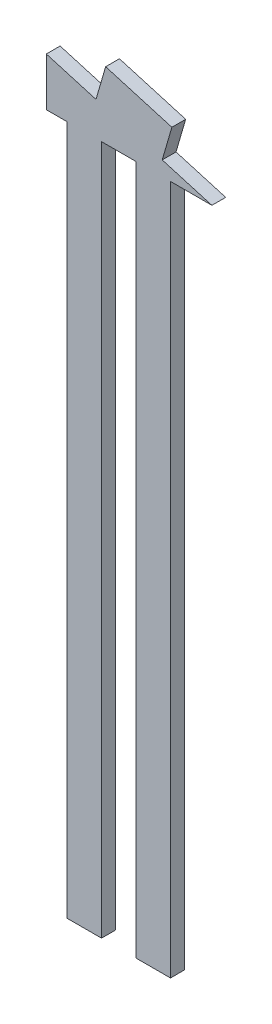
SolidWorks part; units mm, degrees
material "Thornel Mat VMA"
ref_plane "Ön Düzlem" through (0, 0, 0) normal (0, 0, 1) x (1, 0, 0)
ref_plane "Üst Düzlem" through (0, 0, 0) normal (0, 1, 0) x (1, 0, 0)
ref_plane "Sağ Düzlem" through (0, 0, 0) normal (1, 0, 0) x (0, 0, -1)
sketch "Sketch1" plane through (0, 0, 0) normal (0, 0, 1) x (1, 0, 0)
  line L0 (0, 0) -> (24, 0)
  line L1 (24, 0) -> (0, 7)
  line L2 (0, 7) -> (0, 0)
  line L3 (7.2, 4.9) -> (16.8, 2.1)
  line L4 (3, 0) -> (8, 0)
  line L5 (3, 0) -> (3, -100)
  line L6 (3, -100) -> (8, -100)
  line L7 (8, 0) -> (8, -100)
  line L8 (13, 0) -> (18, 0)
  line L9 (13, 0) -> (13, -100)
  line L10 (13, -100) -> (18, -100)
  line L11 (18, 0) -> (18, -100)
  line L12 (7.2, 4.9) -> (8.6, 9.7)
  line L13 (16.8, 2.1) -> (18.2, 6.9)
  line L14 (8.6, 9.7) -> (18.2, 6.9)
  dimension "D1" = 24
  dimension "D2" = 7
  dimension "D3" = 3
  dimension "D4" = 5
  dimension "D5" = 100
  dimension "D6" = 5
  dimension "D7" = 5
  dimension "D8" = 100
  dimension "D9" = 7.5
  dimension "D10" = 10
  dimension "D11" = 5
extrude "Boss-Extrude1" add sketch "Sketch1" along normal blind 2 contours L7 L0 L5 L6 | L11 L0 L9 L10 | L1 L2 L0 | L14 L13 L3 L12 region at (8, 2.3333, 0) region at (5.5, -50, 0) region at (15.5, -50, 0)
